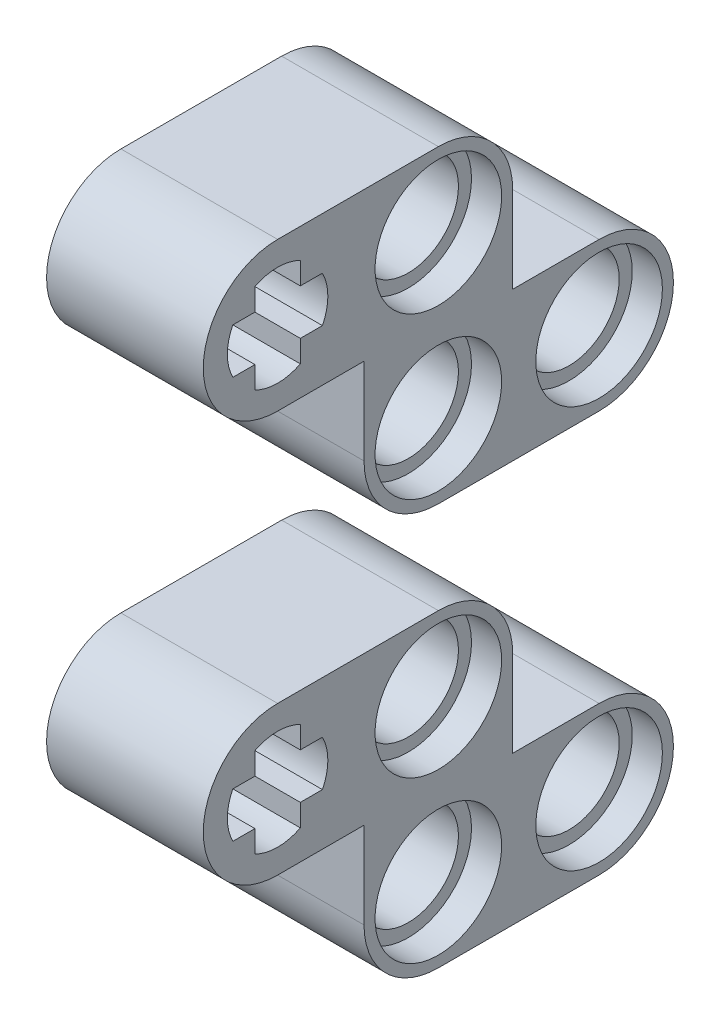
SolidWorks part; units mm, degrees
ref_plane "前视基准面" through (0, 0, 0) normal (0, 0, 1) x (1, 0, 0)
ref_plane "上视基准面" through (0, 0, 0) normal (0, 1, 0) x (1, 0, 0)
ref_plane "右视基准面" through (0, 0, 0) normal (1, 0, 0) x (0, 0, -1)
other "Configuration Table"
sketch "草图1" plane through (0, 0, 0) normal (1, 0, 0) x (0, 0, -1)
  line L0 (8, 0) -> (8, -8) construction
  line L1 (8, -8) -> (16, -8) construction
  line L2 (0, 0) -> (8, 0) construction
  line L3 (-2.23, 1.13) -> (-1.13, 1.13)
  line L4 (-1.13, -2.23) -> (1.13, -2.23)
  line L5 (-1.13, -2.23) -> (-1.13, 2.23)
  line L6 (-1.13, 2.23) -> (1.13, 2.23)
  line L7 (1.13, -2.23) -> (1.13, 2.23)
  line L8 (-1.13, -2.23) -> (1.13, 2.23) construction
  line L9 (-1.13, 2.23) -> (1.13, -2.23) construction
  line L10 (-2.23, -1.13) -> (2.23, -1.13)
  line L11 (-2.23, -1.13) -> (-2.23, 1.13)
  line L12 (-2.23, 1.13) -> (2.23, 1.13)
  line L13 (2.23, -1.13) -> (2.23, 1.13)
  line L14 (-2.23, -1.13) -> (2.23, 1.13) construction
  line L15 (-2.23, 1.13) -> (2.23, -1.13) construction
  line L17 (0, 3.7) -> (8, 3.7)
  line L18 (0, 3.7) -> (0, -3.7)
  line L19 (0, -3.7) -> (8, -3.7)
  line L20 (8, 3.7) -> (8, -3.7)
  line L21 (11.7, 0) -> (4.3, 0)
  line L22 (11.7, 0) -> (11.7, -8)
  line L23 (11.7, -8) -> (4.3, -8)
  line L24 (4.3, 0) -> (4.3, -8)
  line L25 (8, -11.7) -> (16, -11.7)
  line L26 (8, -11.7) -> (8, -4.3)
  line L27 (8, -4.3) -> (16, -4.3)
  line L28 (16, -11.7) -> (16, -4.3)
  circle A0 centre (0, 0) radius 2.5
  circle A1 centre (8, 0) radius 2.5
  circle A2 centre (8, 0) radius 3.15
  circle A3 centre (8, -8) radius 2.5
  circle A4 centre (8, -8) radius 3.15
  circle A5 centre (16, -8) radius 2.5
  circle A6 centre (16, -8) radius 3.15
  circle A7 centre (8, 0) radius 3.7
  circle A8 centre (8, -8) radius 3.7
  circle A9 centre (16, -8) radius 3.7
  circle A10 centre (0, 0) radius 3.15
  circle A11 centre (0, 0) radius 3.7
  dimension "D1" = 5
  dimension "D2" = 6.3
  dimension "D3" = 7.4
  dimension "D4" = 8
  dimension "D5" = 1.1
extrude "凸台-拉伸1" add sketch "草图1" along normal blind 7.8 contours A11 | L17 L20 L19 L18 | A7 | L22 L23 L24 L21 | L27 L28 L25 L26 | A9 | A8
extrude "切除-拉伸1" cut sketch "草图1<3>" along normal through all contours L28 A5 | L28 A5 | L23 A3 L26 | L26 A3 L23 | L26 A3 L23 | L23 A3 L26 | L21 A1 L20 | L20 A1 L21 | L21 A1 L20 | L20 A1 L21 | L6 A0 L18 | L18 A0 L6 | L11 A0 | L4 A0 L18 | L18 A0 L4 | L13 A0 | L5 L6 L7 L4 | L12 L13 L10 L11 region at (0, 0, 2.3385) region at (0, 2.3385, 0.427) region at (0, -2.3385, 0.427) region at (0, 2.3385, -0.427) region at (0, -2.3385, -0.427) region at (0, 0, -2.3385) region at (0, 1.061, -9.061) region at (0, 1.061, -6.939) region at (0, -1.061, -9.061) region at (0, -1.061, -6.939) region at (0, -6.939, -6.939) region at (0, -9.061, -6.939) region at (0, -6.939, -9.061) region at (0, -9.061, -9.061) region at (0, -8, -17.061) region at (0, -8, -14.939)
sketch "草图1<3>" plane through (0, 0, 0) normal (1, 0, 0) x (0, 0, -1) same geometry as "草图1"
extrude "切除-拉伸2" cut sketch "草图1<4>" along normal blind 1.5 contours L28 A6 A5 | L28 A6 A5 | L23 A4 L26 A3 | L26 A4 L23 A3 | L23 A4 L26 A3 | L26 A4 L23 A3 | L21 A2 L20 A1 | L20 A2 L21 A1 | L21 A2 L20 A1 | L20 A2 L21 A1 region at (0, 1.8064, -9.8064) region at (0, 1.8064, -6.1936) region at (0, -1.8064, -9.8064) region at (0, -1.8064, -6.1936) region at (0, -6.1936, -6.1936) region at (0, -9.8064, -6.1936) region at (0, -6.1936, -9.8064) region at (0, -9.8064, -9.8064) region at (0, -5.8224, -18.1776) region at (0, -5.175, -15.9296)
sketch "草图1<4>" plane through (0, 0, 0) normal (1, 0, 0) x (0, 0, -1) same geometry as "草图1"
extrude "切除-拉伸3" cut sketch "草图1<5>" against normal blind 1.5 from surface contours L28 A6 A5 | L28 A6 A5 | L23 A4 L26 A3 | L26 A4 L23 A3 | L23 A4 L26 A3 | L26 A4 L23 A3 | L20 A2 L21 A1 | L21 A2 L20 A1 | L20 A2 L21 A1 | L21 A2 L20 A1 region at (0, 1.8064, -9.8064) region at (0, 1.8064, -6.1936) region at (0, -1.8064, -9.8064) region at (0, -1.8064, -6.1936) region at (0, -6.1936, -6.1936) region at (0, -9.8064, -6.1936) region at (0, -6.1936, -9.8064) region at (0, -9.8064, -9.8064) region at (0, -5.8224, -18.1776) region at (0, -5.175, -15.9296) starting at face at (7.8, -8, -10.5)
sketch "草图1<5>" plane through (0, 0, 0) normal (1, 0, 0) x (0, 0, -1) same geometry as "草图1"
pattern_linear "阵列(线性)1" count 2 spacing 20 along (0, 1, 0) of bodies 109
